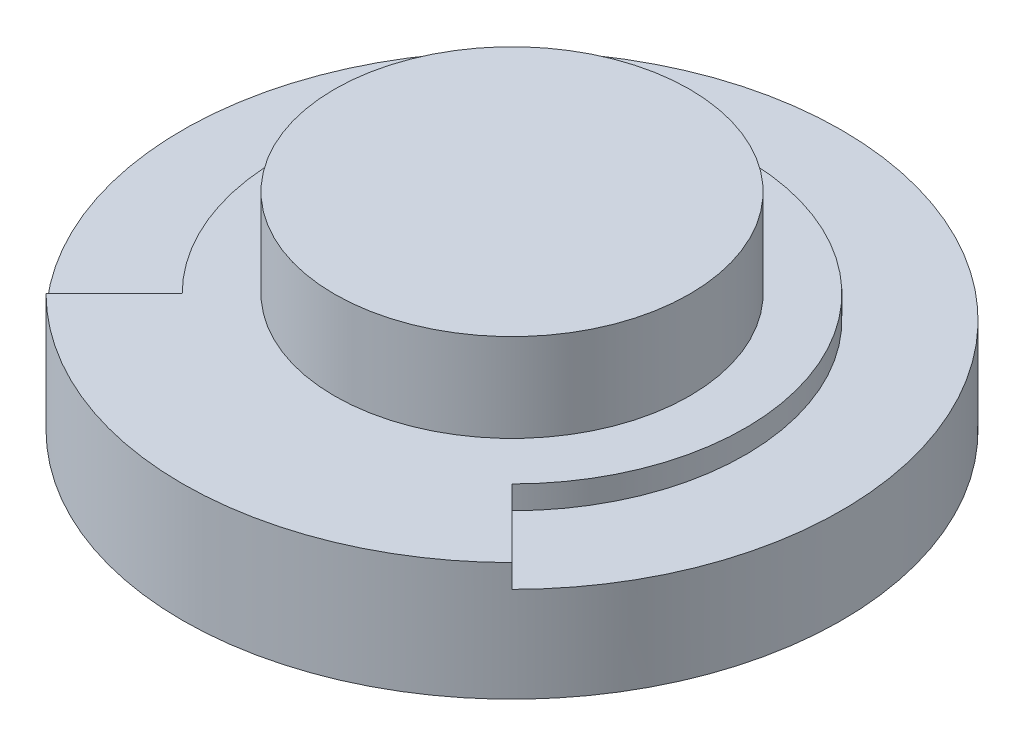
SolidWorks part; units mm, degrees
ref_plane "前视基准面" through (0, 0, 0) normal (0, 0, 1) x (1, 0, 0)
ref_plane "上视基准面" through (0, 0, 0) normal (0, 1, 0) x (1, 0, 0)
ref_plane "右视基准面" through (0, 0, 0) normal (1, 0, 0) x (0, 0, -1)
other "Configuration Table"
sketch "草图1" plane through (0, 0, 0) normal (0, 1, 0) x (1, 0, 0)
  circle A0 centre (0, 0) radius 14.2
  dimension "D1" = 28.4
extrude "凸台-拉伸1" add sketch "草图1" along normal blind 4.1
sketch "草图2" plane through (0, 4.1, 0) normal (0, 1, 0) x (1, 0, 0)
  line L0 (0, 0) -> (-10.0409, -10.0409)
  line L1 (0, 0) -> (10.0409, -10.0409)
  line L2 (0, 0) -> (14.2, 0)
  circle A0 centre (0, 0) radius 10.05
  circle A1 centre (0, 0) radius 7.65
  circle A2 centre (0, 0) radius 14.2 construction
  circle M1 centre (0, 0) radius 14.2
  dimension "D1" = 20.1
  dimension "D2" = 15.3
  dimension "D3" = 90
  dimension "D4" = 45
extrude "凸台-拉伸2" add sketch "草图2" along normal blind 1 contours A0 L0 L1 M1 | A0 region at (0, 4.1, 11.0229)
extrude "凸台-拉伸3" add sketch "草图2<4>" along normal blind 4.8 contours A1
sketch "草图2<4>" plane through (0, 4.1, 0) normal (0, 1, 0) x (1, 0, 0) same geometry as "草图2"
